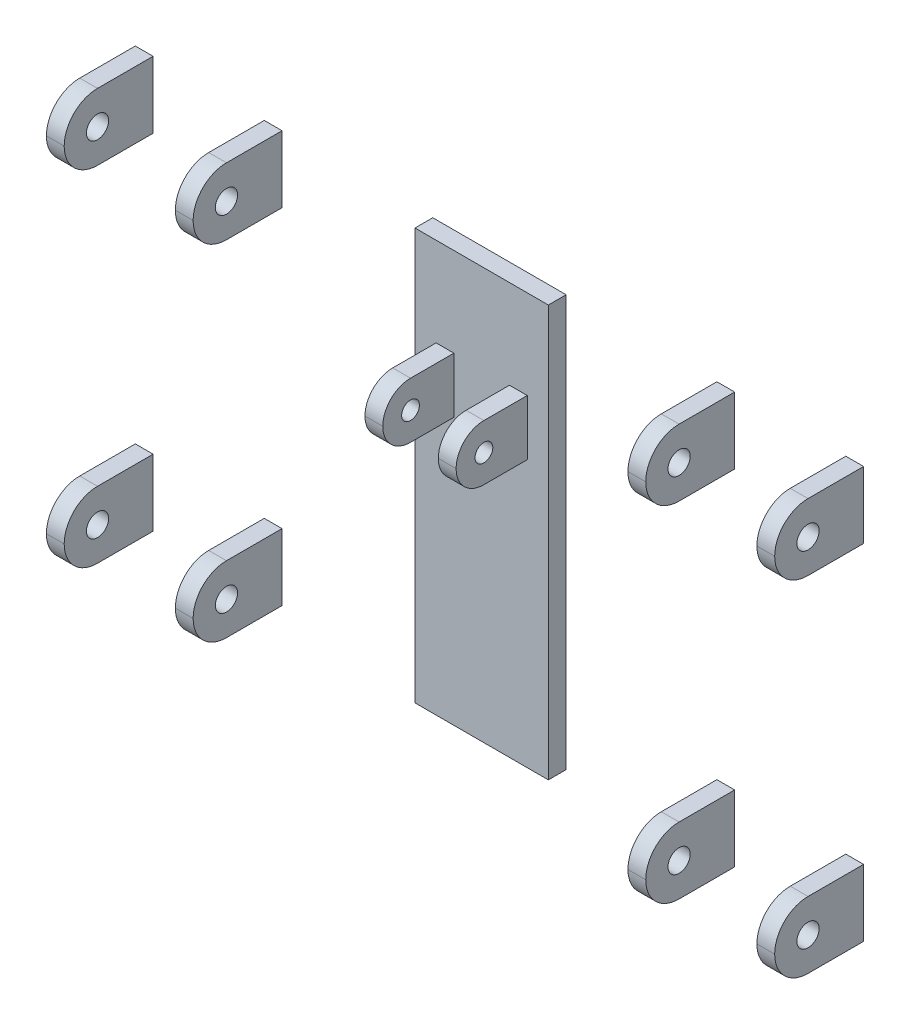
SolidWorks part; units mm, degrees
ref_plane "Front Plane" through (0, 0, 0) normal (0, 0, 1) x (1, 0, 0)
ref_plane "Top Plane" through (0, 0, 0) normal (0, 1, 0) x (1, 0, 0)
ref_plane "Right Plane" through (0, 0, 0) normal (1, 0, 0) x (0, 0, -1)
sketch "Sketch1" plane through (0, 0, 0) normal (0, 0, 1) x (1, 0, 0)
  line L0 (-130.795, 92.5) -> (-130.795, 62.5) construction
  line L5 (-105.795, 92.5) -> (-97.795, 92.5)
  line L6 (-105.795, 92.5) -> (-105.795, 62.5)
  line L7 (-105.795, 62.5) -> (-97.795, 62.5)
  line L8 (-97.795, 92.5) -> (-97.795, 62.5)
  line L9 (-97.795, 92.5) -> (-163.795, 92.5)
  line L10 (-97.795, 92.5) -> (-97.795, 62.5)
  line L11 (-97.795, 62.5) -> (-163.795, 62.5)
  line L12 (-163.795, 92.5) -> (-163.795, 62.5)
  line L13 (-155.795, 62.5) -> (-163.795, 62.5)
  line L14 (-163.795, 92.5) -> (-163.795, 62.5)
  line L15 (-155.795, 92.5) -> (-163.795, 92.5)
  line L16 (-155.795, 92.5) -> (-155.795, 62.5)
  line L17 (0, 150) -> (0, -150) construction
  line L18 (0, 87.5) -> (0, 67.5) construction
  line L20 (130.795, 92.5) -> (130.795, 62.5) construction
  line L21 (155.795, 92.5) -> (155.795, 62.5)
  line L22 (155.795, 92.5) -> (163.795, 92.5)
  line L23 (163.795, 92.5) -> (163.795, 62.5)
  line L24 (155.795, 62.5) -> (163.795, 62.5)
  line L25 (163.795, 92.5) -> (163.795, 62.5)
  line L26 (97.795, 62.5) -> (163.795, 62.5)
  line L27 (97.795, 92.5) -> (97.795, 62.5)
  line L28 (97.795, 92.5) -> (163.795, 92.5)
  line L29 (97.795, 92.5) -> (97.795, 62.5)
  line L30 (105.795, 62.5) -> (97.795, 62.5)
  line L31 (105.795, 92.5) -> (105.795, 62.5)
  line L32 (105.795, 92.5) -> (97.795, 92.5)
  line L34 (-116.6535, 0) -> (75.5924, 0) construction
  line L35 (130.795, -92.5) -> (130.795, -62.5) construction
  line L36 (105.795, -92.5) -> (97.795, -92.5)
  line L37 (105.795, -92.5) -> (105.795, -62.5)
  line L38 (105.795, -62.5) -> (97.795, -62.5)
  line L39 (97.795, -92.5) -> (97.795, -62.5)
  line L40 (97.795, -92.5) -> (163.795, -92.5)
  line L41 (97.795, -92.5) -> (97.795, -62.5)
  line L42 (97.795, -62.5) -> (163.795, -62.5)
  line L43 (163.795, -92.5) -> (163.795, -62.5)
  line L44 (155.795, -62.5) -> (163.795, -62.5)
  line L45 (163.795, -92.5) -> (163.795, -62.5)
  line L46 (155.795, -92.5) -> (163.795, -92.5)
  line L47 (155.795, -92.5) -> (155.795, -62.5)
  line L48 (-130.795, -92.5) -> (-130.795, -62.5) construction
  line L49 (-155.795, -92.5) -> (-155.795, -62.5)
  line L50 (-155.795, -92.5) -> (-163.795, -92.5)
  line L51 (-163.795, -92.5) -> (-163.795, -62.5)
  line L52 (-155.795, -62.5) -> (-163.795, -62.5)
  line L53 (-163.795, -92.5) -> (-163.795, -62.5)
  line L54 (-97.795, -62.5) -> (-163.795, -62.5)
  line L55 (-97.795, -92.5) -> (-97.795, -62.5)
  line L56 (-97.795, -92.5) -> (-163.795, -92.5)
  line L57 (-97.795, -92.5) -> (-97.795, -62.5)
  line L58 (-105.795, -62.5) -> (-97.795, -62.5)
  line L59 (-105.795, -92.5) -> (-105.795, -62.5)
  line L60 (-105.795, -92.5) -> (-97.795, -92.5)
  line L63 (12.5, 87.5) -> (20.5, 87.5)
  line L64 (12.5, 87.5) -> (12.5, 67.5)
  line L65 (12.5, 67.5) -> (20.5, 67.5)
  line L66 (20.5, 87.5) -> (20.5, 67.5)
  line L67 (20.5, 87.5) -> (-20.5, 87.5)
  line L68 (20.5, 87.5) -> (20.5, 67.5)
  line L69 (20.5, 67.5) -> (-20.5, 67.5)
  line L70 (-20.5, 87.5) -> (-20.5, 67.5)
  line L71 (-12.5, 67.5) -> (-20.5, 67.5)
  line L72 (-20.5, 87.5) -> (-20.5, 67.5)
  line L73 (-12.5, 87.5) -> (-20.5, 87.5)
  line L74 (-12.5, 87.5) -> (-12.5, 67.5)
  line L75 (12.5, 87.5) -> (12.5, 67.5)
  line L76 (12.5, 87.5) -> (20.5, 87.5)
  line L77 (20.5, 87.5) -> (20.5, 67.5)
  line L78 (12.5, 67.5) -> (20.5, 67.5)
  line L79 (20.5, 87.5) -> (20.5, 67.5)
  line L80 (-20.5, 87.5) -> (-20.5, 67.5)
  line L81 (-20.5, 87.5) -> (-20.5, 67.5)
  line L82 (-12.5, 67.5) -> (-20.5, 67.5)
  line L83 (-12.5, 87.5) -> (-12.5, 67.5)
  line L84 (-12.5, 87.5) -> (-20.5, 87.5)
  line L85 (0, -87.5) -> (0, -67.5) construction
  line L86 (-12.5, -87.5) -> (-20.5, -87.5)
  line L87 (-12.5, -87.5) -> (-12.5, -67.5)
  line L88 (-12.5, -67.5) -> (-20.5, -67.5)
  line L89 (-20.5, -87.5) -> (-20.5, -67.5)
  line L90 (-20.5, -87.5) -> (-20.5, -67.5)
  line L91 (20.5, -87.5) -> (20.5, -67.5)
  line L92 (12.5, -67.5) -> (20.5, -67.5)
  line L93 (20.5, -87.5) -> (20.5, -67.5)
  line L94 (12.5, -87.5) -> (20.5, -87.5)
  line L95 (12.5, -87.5) -> (12.5, -67.5)
  line L96 (-12.5, -87.5) -> (-12.5, -67.5)
  line L97 (-12.5, -87.5) -> (-20.5, -87.5)
  line L98 (-20.5, -87.5) -> (-20.5, -67.5)
  line L99 (-12.5, -67.5) -> (-20.5, -67.5)
  line L100 (-20.5, -87.5) -> (-20.5, -67.5)
  line L101 (20.5, -67.5) -> (-20.5, -67.5)
  line L102 (20.5, -87.5) -> (20.5, -67.5)
  line L103 (20.5, -87.5) -> (-20.5, -87.5)
  line L104 (20.5, -87.5) -> (20.5, -67.5)
  line L105 (12.5, -67.5) -> (20.5, -67.5)
  line L106 (12.5, -87.5) -> (12.5, -67.5)
  line L107 (12.5, -87.5) -> (20.5, -87.5)
  dimension "D1" = 8
  dimension "D2" = 30
  dimension "D3" = 50
  dimension "D4" = 311.59
  dimension "D5" = 92.5
  dimension "D6" = 8
  dimension "D7" = 20
  dimension "D8" = 25
  dimension "D9" = 5
extrude "Boss-Extrude1" add sketch "Sketch1" along normal blind 40 contours L16 L9 L12 L11 | L8 L5 L6 L7 | L31 L28 L27 L26 | L21 L24 L23 L22 | L47 L40 L43 L42 | L39 L36 L37 L38 | L59 L56 L55 L54 | L49 L52 L51 L50 region at (-101.795, 77.5, 0) region at (-159.795, 77.5, 0) region at (159.795, 77.5, 0) region at (101.795, 77.5, 0) region at (101.795, -77.5, 0) region at (159.795, -77.5, 0) region at (-159.795, -77.5, 0) region at (-101.795, -77.5, 0)
fillet "Fillet1" radius 15 2 edges at (-159.795, 62.5, 40) (-159.795, 92.5, 40)
fillet "Fillet2" radius 15 2 edges at (-101.795, 62.5, 40) (-101.795, 92.5, 40)
fillet "Fillet3" radius 15 2 edges at (101.795, 62.5, 40) (101.795, 92.5, 40)
fillet "Fillet4" radius 15 2 edges at (159.795, 62.5, 40) (159.795, 92.5, 40)
fillet "Fillet5" radius 15 2 edges at (-159.795, -92.5, 40) (-159.795, -62.5, 40)
fillet "Fillet6" radius 15 2 edges at (-101.795, -92.5, 40) (-101.795, -62.5, 40)
fillet "Fillet7" radius 15 2 edges at (101.795, -92.5, 40) (101.795, -62.5, 40)
fillet "Fillet8" radius 15 2 edges at (159.795, -92.5, 40) (159.795, -62.5, 40)
sketch "Sketch4" plane through (-163.795, 0, 0) normal (-1, 0, 0) x (0, 0, 1)
  circle A0 centre (25, -77.5) radius 5
  arc A1 (40, -77.5) -> (25, -62.5) centre (25, -77.5) ccw construction
  dimension "D1" = 10
extrude "Cut-Extrude2" cut sketch "Sketch4" against normal through all
sketch "Sketch3" plane through (-163.795, 0, 0) normal (-1, 0, 0) x (0, 0, 1)
  circle A0 centre (25, 77.5) radius 5
  arc A2 (40, 77.5) -> (25, 92.5) centre (25, 77.5) ccw construction
  dimension "D1" = 10
extrude "Cut-Extrude1" cut sketch "Sketch3" against normal through all
sketch "Sketch5" plane through (0, 0, 0) normal (0, 0, -1) x (-1, 0, 0)
  line L0 (105.795, 92.5) -> (97.795, 92.5) construction
  line L1 (30, 92.5) -> (-30, 92.5)
  line L2 (30, 92.5) -> (30, -92.5)
  line L3 (30, -92.5) -> (-30, -92.5)
  line L4 (-30, 92.5) -> (-30, -92.5)
  line L5 (97.795, -92.5) -> (105.795, -92.5) construction
  line L6 (0, 92.5) -> (0, -92.5) construction
  dimension "D1" = 60
extrude "Boss-Extrude2" add sketch "Sketch5" against normal blind 8 separate body
sketch "Sketch6" plane through (0, 0, 0) normal (0, 0, -1) x (-1, 0, 0)
  line L0 (0, 52.5) -> (0, 27.5) construction
  line L1 (-20.5, 52.5) -> (-12.5, 52.5)
  line L2 (-20.5, 52.5) -> (-20.5, 27.5)
  line L3 (-20.5, 27.5) -> (-12.5, 27.5)
  line L4 (-12.5, 52.5) -> (-12.5, 27.5)
  line L5 (-20.5, 52.5) -> (20.5, 52.5)
  line L6 (-20.5, 52.5) -> (-20.5, 27.5)
  line L7 (-20.5, 27.5) -> (20.5, 27.5)
  line L8 (20.5, 52.5) -> (20.5, 27.5)
  line L10 (20.5, 52.5) -> (20.5, 27.5)
  line L11 (12.5, 52.5) -> (12.5, 27.5)
  line L12 (20.5, 27.5) -> (12.5, 27.5)
  line L13 (20.5, 52.5) -> (12.5, 52.5)
  line L14 (20.5, 52.5) -> (20.5, 27.5)
  line L16 (30, 92.5) -> (-30, 92.5) construction
  dimension "D1" = 8
  dimension "D2" = 41
  dimension "D3" = 25
  dimension "D4" = 40
extrude "Boss-Extrude3" add sketch "Sketch6" against normal blind 40 contours L5 L11 L7 L8 | L4 L1 L2 L3 region at (16.5, 40, 0) region at (-16.5, 40, 0)
fillet "Fillet9" radius 12.5 4 edges at (16.5, 52.5, 40) (16.5, 27.5, 40) (-16.5, 52.5, 40) (-16.5, 27.5, 40)
sketch "Sketch7" plane through (-20.5, 0, 0) normal (-1, 0, 0) x (0, 0, 1)
  circle A0 centre (27.5, 40) radius 4
  arc A1 (40, 40) -> (27.5, 52.5) centre (27.5, 40) ccw construction
  dimension "D1" = 8
extrude "Cut-Extrude3" cut sketch "Sketch7" against normal through all
